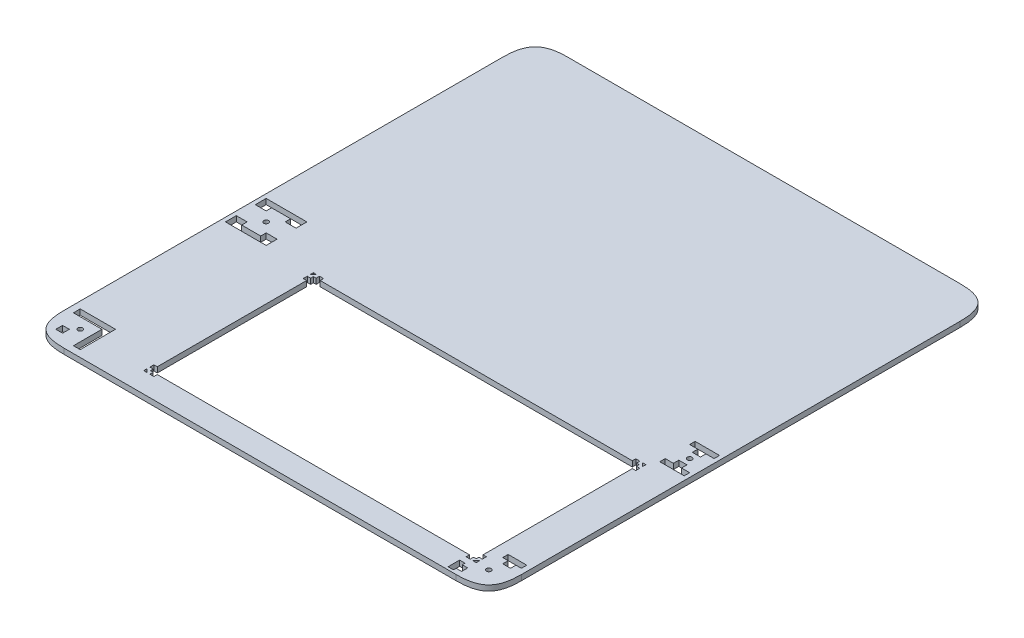
SolidWorks part; units mm, degrees
ref_plane "Front Plane" through (0, 0, 0) normal (0, 0, 1) x (1, 0, 0)
ref_plane "Top Plane" through (0, 0, 0) normal (0, 1, 0) x (1, 0, 0)
ref_plane "Right Plane" through (0, 0, 0) normal (1, 0, 0) x (0, 0, -1)
sketch "Sketch1" plane through (0, 0, 0) normal (0, 1, 0) x (1, 0, 0)
  line L1 (0, 0) -> (337, 0)
  line L2 (0, 0) -> (0, 371.22)
  line L3 (0, 371.22) -> (337, 371.22)
  line L4 (337, 0) -> (337, 371.22)
  line L5 (70.28, 137.5) -> (310.28, 137.5)
  line L6 (70.28, 137.5) -> (70.28, 17.5)
  line L7 (70.28, 17.5) -> (310.28, 17.5)
  line L8 (310.28, 137.5) -> (310.28, 17.5)
  dimension "D1" = 337
  dimension "D2" = 371.22
  dimension "D3" = 240
  dimension "D4" = 120
  dimension "D5" = 17.5
  dimension "D6" = 26.72
extrude "Boss-Extrude1" add sketch "Sketch1" against normal blind 4
fillet "Fillet1" radius 24 4 edges at (0, -2, 0) (337, -2, 0) (0, -2, -371.22) (337, -2, -371.22) conic rho 0.55
sketch "Sketch3" plane through (0, 0, 0) normal (0, 1, 0) x (1, 0, 0)
  line L0 (337, 24) -> (337, 347.22) construction
  line L1 (24, 0) -> (313, 0) construction
  line L2 (0, 347.22) -> (0, 24) construction
  line L3 (309, 4) -> (309, 2)
  line L4 (305, 10.5) -> (309, 10.5)
  line L5 (305, 10.5) -> (305, 2)
  line L6 (305, 2) -> (309, 2)
  line L7 (309, 10.5) -> (309, 8.5)
  line L8 (309, 8.5) -> (313, 8.5)
  line L10 (309, 4) -> (313, 4)
  line L11 (313, 8.5) -> (313, 4)
  line L12 (329, 28) -> (333, 28)
  line L13 (319.28, 32) -> (333, 32)
  line L14 (319.28, 32) -> (319.28, 28)
  line L15 (319.28, 28) -> (323.28, 28)
  line L16 (333, 32) -> (333, 28)
  line L18 (323.28, 28) -> (323.28, 24)
  line L19 (323.28, 24) -> (329, 24)
  line L20 (329, 28) -> (329, 24)
  line L21 (328, 151) -> (334, 151)
  line L30 (26, 5) -> (31, 5)
  line L36 (26, 5) -> (26, 26)
  line L37 (9, 14) -> (14, 14)
  line L38 (9, 14) -> (9, 9)
  line L39 (9, 9) -> (14, 9)
  line L40 (14, 14) -> (14, 9)
  line L41 (26, 31) -> (31, 31)
  line L42 (31, 5) -> (31, 31)
  line L43 (26, 31) -> (5, 31)
  line L45 (26, 26) -> (5, 26)
  line L46 (5, 31) -> (5, 26)
  line L47 (3, 140) -> (33, 140)
  line L48 (3, 140) -> (3, 144)
  line L49 (11, 144) -> (25, 144)
  line L50 (33, 140) -> (33, 144)
  line L52 (3, 144) -> (3, 148)
  line L53 (3, 148) -> (11, 148)
  line L54 (11, 144) -> (11, 148)
  line L56 (33, 144) -> (33, 148)
  line L57 (33, 148) -> (25, 148)
  line L58 (25, 144) -> (25, 148)
  line L59 (3, 170) -> (33, 170)
  line L60 (3, 170) -> (3, 166)
  line L61 (11, 166) -> (25, 166)
  line L62 (33, 170) -> (33, 166)
  line L64 (3, 166) -> (3, 162)
  line L65 (3, 162) -> (11, 162)
  line L66 (11, 166) -> (11, 162)
  line L68 (33, 166) -> (33, 162)
  line L69 (33, 162) -> (25, 162)
  line L70 (25, 166) -> (25, 162)
  line L71 (316, 147) -> (334, 147)
  line L72 (316, 147) -> (316, 151)
  line L73 (316, 151) -> (322, 151)
  line L74 (334, 147) -> (334, 151)
  line L76 (322, 151) -> (322, 155)
  line L77 (322, 155) -> (328, 155)
  line L78 (328, 151) -> (328, 155)
  line L79 (328, 169) -> (334, 169)
  line L80 (316, 173) -> (334, 173)
  line L81 (316, 173) -> (316, 169)
  line L82 (316, 169) -> (322, 169)
  line L83 (334, 173) -> (334, 169)
  line L85 (322, 169) -> (322, 165)
  line L86 (322, 165) -> (328, 165)
  line L87 (328, 169) -> (328, 165)
  circle A0 centre (322, 15) radius 1.75
  circle A1 centre (18, 18) radius 1.75
  circle A2 centre (18, 155) radius 1.75
  circle A3 centre (325, 160) radius 1.75
  point P37 (5, 28.5)
  dimension "D3" = 3.5
  dimension "D6" = 3.5
  dimension "D45" = 3.5
  dimension "D62" = 3.5
  dimension "D1" = 15
  dimension "D2" = 15
  dimension "D4" = 18
  dimension "D5" = 18
  dimension "D7" = 24
  dimension "D8" = 4
  dimension "D9" = 2
  dimension "D10" = 2
  dimension "D11" = 4.5
  dimension "D12" = 2
  dimension "D13" = 4
  dimension "D14" = 4
  dimension "D15" = 13.72
  dimension "D16" = 4
  dimension "D17" = 4
  dimension "D18" = 4
  dimension "D19" = 4
  dimension "D20" = 24
  dimension "D21" = 5
  dimension "D22" = 5
  dimension "D23" = 9
  dimension "D24" = 9
  dimension "D25" = 26
  dimension "D26" = 5
  dimension "D27" = 5
  dimension "D28" = 5
  dimension "D29" = 21
  dimension "D30" = 5
  dimension "D31" = 30
  dimension "D32" = 4
  dimension "D33" = 4
  dimension "D34" = 8
  dimension "D35" = 8
  dimension "D36" = 4
  dimension "D37" = 30
  dimension "D38" = 4
  dimension "D39" = 4
  dimension "D40" = 4
  dimension "D41" = 30
  dimension "D42" = 140
  dimension "D43" = 3
  dimension "D44" = 3
  dimension "D46" = 11
  dimension "D47" = 4
  dimension "D48" = 4
  dimension "D49" = 4
  dimension "D50" = 18
  dimension "D51" = 3
  dimension "D52" = 6
  dimension "D53" = 6
  dimension "D54" = 4
  dimension "D55" = 4
  dimension "D56" = 4
  dimension "D57" = 18
  dimension "D58" = 6
  dimension "D59" = 6
  dimension "D60" = 10
  dimension "D61" = 147
  dimension "D63" = 5
  dimension "D64" = 9
extrude "Cut-Extrude1" cut sketch "Sketch3" against normal up to next
ref_plane "Plane3" through (190.28, 0, 0) normal (-1, 0, 0) x (0, 0, 1)
ref_plane "Plane6" through (0, 0, -77.5) normal (0, 0, 1) x (1, 0, 0)
sketch "Sketch5" plane through (0, 0, 0) normal (0, 1, 0) x (1, 0, 0)
  line L0 (310.28, 17.5) -> (310.28, 137.5) construction
  line L3 (310.28, 15) -> (312.78, 15)
  line L4 (312.78, 17.5) -> (312.78, 15)
  line L5 (310.28, 22.5) -> (312.78, 22.5)
  line L6 (310.28, 22.5) -> (310.28, 19.5)
  line L7 (310.28, 19.5) -> (312.78, 19.5)
  line L8 (312.78, 22.5) -> (312.78, 19.5)
  line L9 (70.28, 17.5) -> (310.28, 17.5) construction
  line L10 (305.28, 17.5) -> (308.28, 17.5)
  line L11 (305.28, 17.5) -> (305.28, 15)
  line L12 (305.28, 15) -> (308.28, 15)
  line L13 (308.28, 17.5) -> (308.28, 15)
  line L14 (310.28, 15) -> (312.78, 17.5)
  dimension "D1" = 2.5
  dimension "D2" = 2.5
  dimension "D4" = 3
  dimension "D6" = 3
extrude "Cut-Extrude2" cut sketch "Sketch5" against normal up to next
mirror "Mirror1" about plane through (0, 0, -77.5) normal (0, 0, 1) of "Cut-Extrude2" second plane through (190.28, 0, 0) second plane normal (-1, 0, 0)
